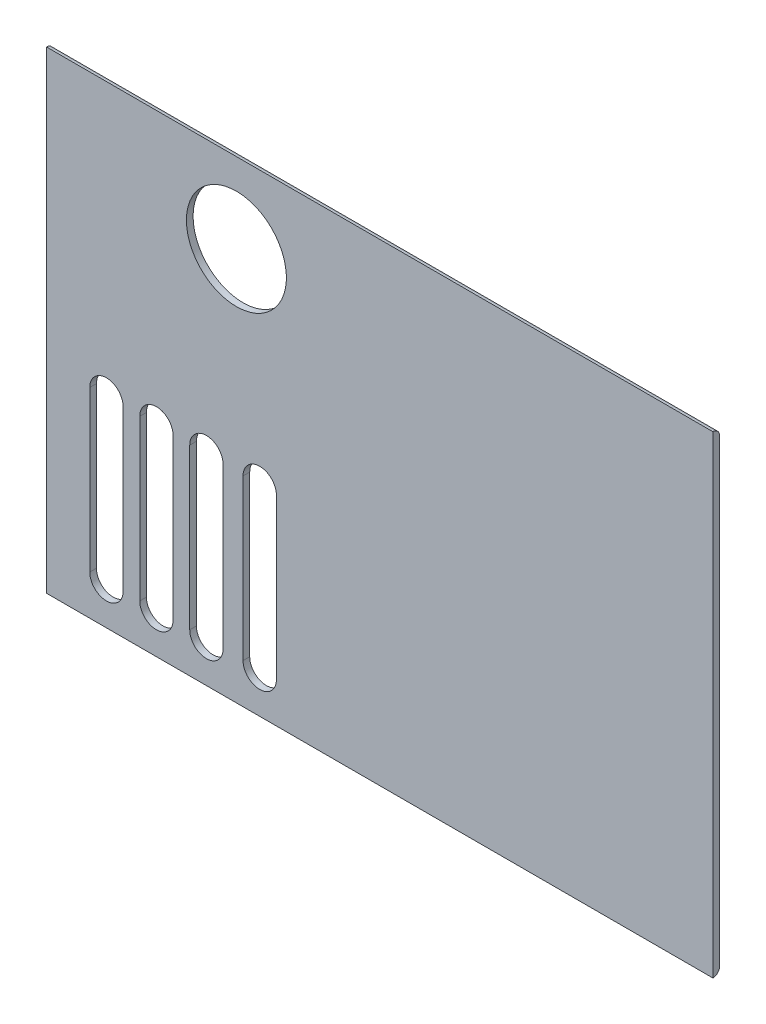
SolidWorks part; units mm, degrees
ref_plane "Front Plane" through (0, 0, 0) normal (0, 0, 1) x (1, 0, 0)
ref_plane "Top Plane" through (0, 0, 0) normal (0, 1, 0) x (1, 0, 0)
ref_plane "Right Plane" through (0, 0, 0) normal (1, 0, 0) x (0, 0, -1)
sketch "Sketch1" plane through (0, 0, 0) normal (0, 0, 1) x (1, 0, 0)
  line L1 (100, -85.3987) -> (-100, -85.3987)
  line L2 (100, -85.3987) -> (100, 56.6013)
  line L3 (100, 56.6013) -> (-100, 56.6013)
  line L4 (-100, -85.3987) -> (-100, 56.6013)
  line L5 (100, -85.3987) -> (-100, 56.6013) construction
  line L6 (100, 56.6013) -> (-100, -85.3987) construction
  point P0 (0, -14.3987)
  dimension "D1" = 200
  dimension "D2" = 142
extrude "Boss-Extrude1" add sketch "Sketch1" along normal blind 2
sketch "Sketch2" plane through (0, 0, 2) normal (0, 0, 1) x (1, 0, 0)
  text T0 "this is a test"
extrude "Boss-Extrude2" [suppressed] add sketch "Sketch2" along normal blind 1
sketch "Sketch3" plane through (0, 0, 0) normal (0, 0, -1) x (-1, 0, 0)
  line L0 (100, -49.3987) -> (-100, -49.3987) construction
  line L1 (100, 56.6013) -> (100, -85.3987) construction
  line L2 (-100, -85.3987) -> (-100, 56.6013) construction
  line L3 (67, -73.3987) -> (67, -25.3987) construction
  line L4 (62, -73.3987) -> (62, -25.3987)
  line L5 (72, -73.3987) -> (72, -25.3987)
  line L6 (100, -25.3987) -> (-100, -25.3987) construction
  line L7 (82, -73.3987) -> (82, -25.3987) construction
  line L8 (100, -73.3987) -> (-100, -73.3987) construction
  line L9 (77, -73.3987) -> (77, -25.3987)
  line L10 (87, -73.3987) -> (87, -25.3987)
  line L11 (52, -73.3987) -> (52, -25.3987) construction
  line L12 (47, -73.3987) -> (47, -25.3987)
  line L13 (57, -73.3987) -> (57, -25.3987)
  line L14 (36, -73.3987) -> (36, -25.3987) construction
  line L15 (31, -73.3987) -> (31, -25.3987)
  line L16 (41, -73.3987) -> (41, -25.3987)
  line L18 (-100, 56.6013) -> (100, 56.6013) construction
  line L19 (100, -85.3987) -> (-100, -85.3987) construction
  circle A0 centre (43, 32.6013) radius 15
  arc A1 (62, -73.3987) -> (72, -73.3987) centre (67, -73.3987) ccw
  arc A2 (72, -25.3987) -> (62, -25.3987) centre (67, -25.3987) ccw
  arc A3 (77, -73.3987) -> (87, -73.3987) centre (82, -73.3987) ccw
  arc A4 (87, -25.3987) -> (77, -25.3987) centre (82, -25.3987) ccw
  arc A5 (47, -73.3987) -> (57, -73.3987) centre (52, -73.3987) ccw
  arc A6 (57, -25.3987) -> (47, -25.3987) centre (52, -25.3987) ccw
  arc A7 (31, -73.3987) -> (41, -73.3987) centre (36, -73.3987) ccw
  arc A8 (41, -25.3987) -> (31, -25.3987) centre (36, -25.3987) ccw
  point P10 (67, -49.3987)
  point P21 (82, -49.3987)
  point P27 (52, -49.3987)
  point P34 (36, -49.3987)
  dimension "D1" = 30
  dimension "D2" = 24
  dimension "D3" = 57
  dimension "D4" = 13
  dimension "D5" = 12
  dimension "D6" = 24
  dimension "D8" = 10
  dimension "D9" = 10
  dimension "D10" = 10
  dimension "D11" = 10
  dimension "D12" = 5
  dimension "D13" = 56
  dimension "D14" = 5
extrude "Cut-Extrude1" cut sketch "Sketch3" against normal through all
fillet "Fillet1" radius 2 2 edges at (0, 56.6013, 0) (0, -85.3987, 0)
sketch "Sketch4" plane through (0, 0, 0) normal (0, 0, -1) x (-1, 0, 0)
  line L0 (100, -49.3987) -> (-100, -49.3987) construction
  line L1 (100, -73.3987) -> (-100, -73.3987) construction
  spline S0 degree 3 poles (52.7239, -15.4726) (-14.6287, 13.632) (59.1705, -88.8041) (-16.6563, -73.3987) knots 0 0 0 0 1 1 1 1
  spline S1 degree 2 poles (52.7239, -15.4726) (77.8976, -2.2403) (21.3765, -3.4388) knots 0 0 0 1 1 1
  spline S2 degree 3 poles (-16.6563, -73.3987) (-30.9712, -57.8523) (2.0831, -74.6614) (18.5265, -39.6769) (12.476, -17.3845) (21.3765, -3.4388) knots 0 0 0 0 0.313928 0.520229 1 1 1 1
extrude "Cut-Extrude2" cut sketch "Sketch4" against normal blind 0.01
sketch "Sketch5" plane through (0, 0, 0.01) normal (0, 0, -1) x (-1, 0, 0)
  text T0 "mcHF"
  point P1 (-12.9125, -72.1661)
extrude "Boss-Extrude3" add sketch "Sketch5" along normal blind 0.01
